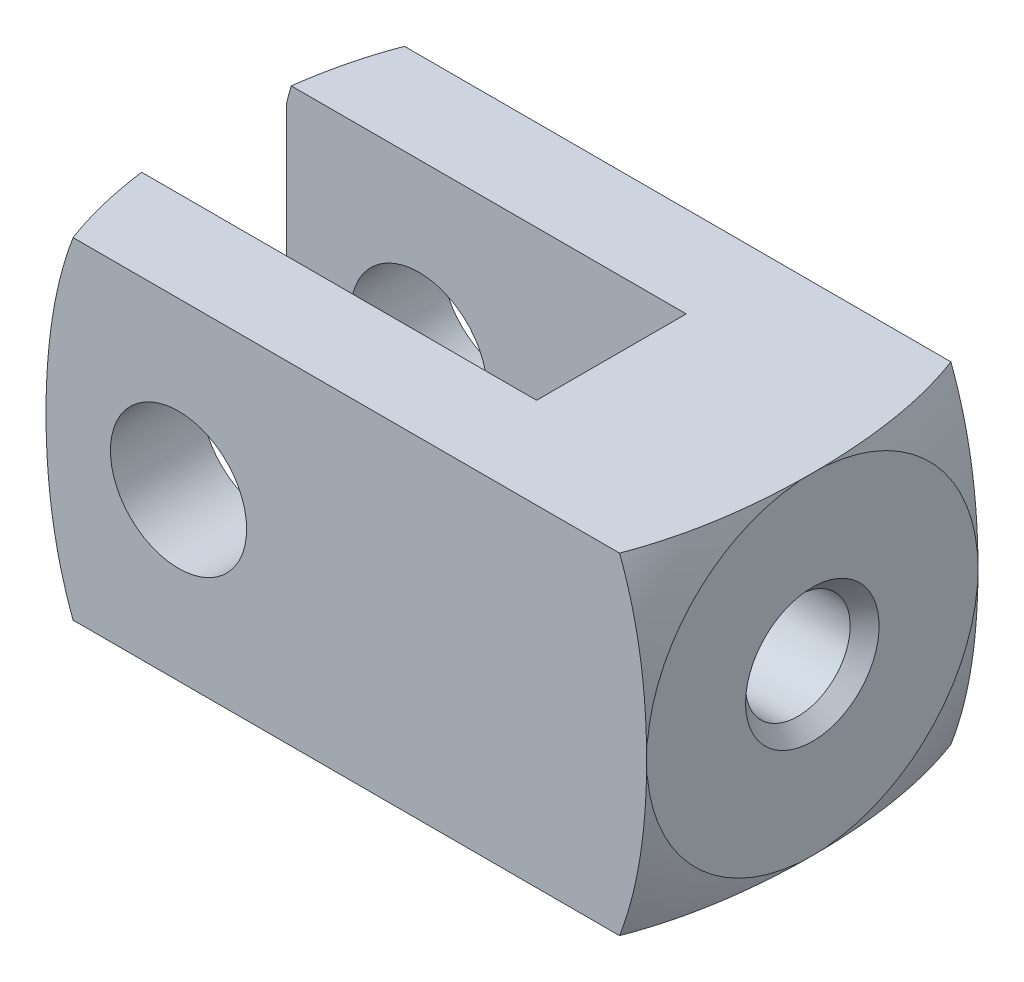
SolidWorks part; units mm, degrees
ref_plane "Front Plane" through (0, 0, 0) normal (0, 0, 1) x (1, 0, 0)
ref_plane "Top Plane" through (0, 0, 0) normal (0, 1, 0) x (1, 0, 0)
ref_plane "Right Plane" through (0, 0, 0) normal (1, 0, 0) x (0, 0, -1)
sketch "Sketch1" plane through (0, 0, 0) normal (0, 0, 1) x (1, 0, 0)
  line L0 (-3.1496, -3.937) -> (11.1252, -3.937)
  line L1 (11.1252, -3.937) -> (11.1252, 3.937)
  line L2 (11.1252, 3.937) -> (-3.1496, 3.937)
  line L3 (-3.1496, 3.937) -> (-3.1496, -3.937)
extrude "Boss-Extrude1" add sketch "Sketch1" against normal blind 3.937 and the other way blind 3.937
sketch "Sketch2" plane through (0, 0, 0) normal (0, 1, 0) x (1, 0, 0)
  line L0 (-3.1496, -1.778) -> (6.35, -1.778)
  line L1 (6.35, -1.778) -> (6.35, 1.778)
  line L2 (6.35, 1.778) -> (-3.1496, 1.778)
  line L3 (-3.1496, 1.778) -> (-3.1496, -1.778)
extrude "Cut-Extrude1" cut sketch "Sketch2" along normal blind 3.937 and the other way blind 3.937
sketch "Sketch3" plane through (0, 0, 0) normal (0, 0, 1) x (1, 0, 0)
  line L0 (6.5532, 0) -> (6.5532, 1.2433)
  line L1 (6.5532, 1.2433) -> (10.781, 1.2433)
  line L2 (10.781, 1.2433) -> (11.1252, 1.5875)
  line L3 (11.1252, 1.5875) -> (11.1252, 0)
  line L4 (11.1252, 0) -> (6.5532, 0)
  line L5 (11.1252, 0) -> (6.5532, 0) construction
revolve "Cut-Revolve1" cut sketch "Sketch3" angle 360 about L5 reverse direction yes
cosmetic thread "Cosmetic Thread1" parameters "D1"=4.572, "D2"=3.175
ref_plane "Plane1" through (0, 0, 6.35) normal (0, 0, 1) x (1, 0, 0)
ref_plane "Plane2" through (0, 0, -6.35) normal (0, 0, 1) x (1, 0, 0)
ref_plane "Plane3" through (23.876, 0, 0) normal (1, 0, 0) x (0, 0, -1)
sketch "Sketch4" plane through (0, 0, 0) normal (0, 0, 1) x (1, 0, 0)
  line L0 (6.35, 0) -> (6.35, 1.2637)
  line L1 (6.35, 1.2637) -> (6.5532, 1.2637)
  line L2 (6.5532, 1.2637) -> (6.5532, 0)
  line L3 (6.5532, 0) -> (6.35, 0)
  line L4 (6.5532, 0) -> (6.35, 0) construction
revolve "Cut-Revolve2" cut sketch "Sketch4" angle 360 about L4 reverse direction yes
sketch "Sketch5" plane through (0, 0, 0) normal (1, 0, 0) x (0, 0, -1)
  line L0 (-3.937, 0) -> (-3.937, 1.6193)
  line L1 (-3.937, 1.6193) -> (3.937, 1.6193)
  line L2 (3.937, 1.6193) -> (3.937, 0)
  line L3 (3.937, 0) -> (-3.937, 0)
  line L4 (3.937, 0) -> (-3.937, 0) construction
revolve "Cut-Revolve3" cut sketch "Sketch5" angle 360 about L4 reverse direction yes
sketch "Sketch6" plane through (0, 0, 0) normal (0, 0, 1) x (1, 0, 0)
  line L0 (11.1252, 0) -> (11.1252, 3.937)
  line L1 (8.5852, 7.874) -> (15.0622, 7.874)
  line L2 (15.0622, 7.874) -> (15.0622, 0)
  line L3 (15.0622, 0) -> (11.1252, 0)
  line L4 (15.0622, 0) -> (11.1252, 0) construction
  arc A0 (11.1252, 3.937) -> (8.5852, 7.874) centre (3.7528, 1.9685) ccw
revolve "Cut-Revolve4" cut sketch "Sketch6" angle 360 about L4 reverse direction yes
sketch "Sketch7" plane through (0, 0, 0) normal (0, 0, 1) x (1, 0, 0)
  line L0 (-7.0866, 0) -> (-7.0866, 7.874)
  line L1 (-7.0866, 7.874) -> (-0.6096, 7.874)
  line L2 (-3.1496, 3.937) -> (-3.1496, 0)
  line L3 (-3.1496, 0) -> (-7.0866, 0)
  line L4 (-3.1496, 0) -> (-7.0866, 0) construction
  arc A0 (-0.6096, 7.874) -> (-3.1496, 3.937) centre (4.2228, 1.9685) ccw
revolve "Cut-Revolve5" cut sketch "Sketch7" angle 360 about L4 reverse direction yes
ref_plane "Plane4" through (11.1252, 0, 0) normal (1, 0, 0) x (0, 0, -1)
ref_plane "Plane5" through (6.35, 0, 0) normal (1, 0, 0) x (0, 0, -1)
ref_plane "dummy XY" through (0, 0, 0) normal (0, 0, 1) x (1, 0, 0)
ref_plane "dummy XZ" through (0, 0, 0) normal (0, -1, 0) x (-1, 0, 0)
ref_plane "dummy YZ" through (0, 0, 0) normal (1, 0, 0) x (0, 0, -1)
ref_axis "dummy X" through (-80.9, 0, 0) along (1, 0, 0)
ref_axis "dummy Y" through (0, -50, 0) along (0, 1, 0)
ref_axis "dummy Z" through (0, 0, 80.9) along (0, 0, -1)
sketch3d "dummy"
  point P0 (0, 0, 0)
ref_plane "h1 XY" through (0, 0, 0) normal (0, 0, 1) x (1, 0, 0)
ref_plane "h1 XZ" through (0, 3.937, 0) normal (0, -1, 0) x (-1, 0, 0)
ref_plane "h1 YZ" through (-3.1496, 0, 0) normal (1, 0, 0) x (0, 0, -1)
ref_axis "h1 X" through (-80.9, 3.937, 0) along (1, 0, 0)
ref_axis "h1 Y" through (-3.1496, -50, 0) along (0, 1, 0)
ref_axis "h1 Z" through (-3.1496, 3.937, 80.9) along (0, 0, -1)
sketch3d "h1"
  point P0 (-3.1496, 3.937, 0)
ref_plane "h2 XY" through (0, 0, 0) normal (0, 0, 1) x (1, 0, 0)
ref_plane "h2 XZ" through (0, -3.937, 0) normal (0, -1, 0) x (-1, 0, 0)
ref_plane "h2 YZ" through (-3.1496, 0, 0) normal (1, 0, 0) x (0, 0, -1)
ref_axis "h2 X" through (-80.9, -3.937, 0) along (1, 0, 0)
ref_axis "h2 Y" through (-3.1496, -50, 0) along (0, 1, 0)
ref_axis "h2 Z" through (-3.1496, -3.937, 80.9) along (0, 0, -1)
sketch3d "h2"
  point P0 (-3.1496, -3.937, 0)
ref_plane "l1 XY" through (0, 0, 0) normal (0, 0, 1) x (1, 0, 0)
ref_plane "l1 XZ" through (0, 3.937, 0) normal (0, -1, 0) x (-1, 0, 0)
ref_plane "l1 YZ" through (11.1252, 0, 0) normal (1, 0, 0) x (0, 0, -1)
ref_axis "l1 X" through (-80.9, 3.937, 0) along (1, 0, 0)
ref_axis "l1 Y" through (11.1252, -50, 0) along (0, 1, 0)
ref_axis "l1 Z" through (11.1252, 3.937, 80.9) along (0, 0, -1)
sketch3d "l1"
  point P0 (11.1252, 3.937, 0)
ref_plane "l11 XY" through (0, 0, 0) normal (0, 0, 1) x (1, 0, 0)
ref_plane "l11 XZ" through (0, 3.937, 0) normal (0, -1, 0) x (-1, 0, 0)
ref_plane "l11 YZ" through (11.1252, 0, 0) normal (1, 0, 0) x (0, 0, -1)
ref_axis "l11 X" through (-80.9, 3.937, 0) along (1, 0, 0)
ref_axis "l11 Y" through (11.1252, -50, 0) along (0, 1, 0)
ref_axis "l11 Z" through (11.1252, 3.937, 80.9) along (0, 0, -1)
sketch3d "l11"
  point P0 (11.1252, 3.937, 0)
ref_plane "l12 XY" through (0, 0, 0) normal (0, 0, 1) x (1, 0, 0)
ref_plane "l12 XZ" through (0, 3.937, 0) normal (0, -1, 0) x (-1, 0, 0)
ref_plane "l12 YZ" through (0, 0, 0) normal (1, 0, 0) x (0, 0, -1)
ref_axis "l12 X" through (-80.9, 3.937, 0) along (1, 0, 0)
ref_axis "l12 Y" through (0, -50, 0) along (0, 1, 0)
ref_axis "l12 Z" through (0, 3.937, 80.9) along (0, 0, -1)
sketch3d "l12"
  point P0 (0, 3.937, 0)
ref_plane "l2 XY" through (0, 0, 0) normal (0, 0, 1) x (1, 0, 0)
ref_plane "l2 XZ" through (0, 3.937, 0) normal (0, -1, 0) x (-1, 0, 0)
ref_plane "l2 YZ" through (-3.1496, 0, 0) normal (1, 0, 0) x (0, 0, -1)
ref_axis "l2 X" through (-80.9, 3.937, 0) along (1, 0, 0)
ref_axis "l2 Y" through (-3.1496, -50, 0) along (0, 1, 0)
ref_axis "l2 Z" through (-3.1496, 3.937, 80.9) along (0, 0, -1)
sketch3d "l2"
  point P0 (-3.1496, 3.937, 0)
ref_plane "l21 XY" through (0, 0, 0) normal (0, 1, 0) x (1, 0, 0)
ref_plane "l21 XZ" through (0, 0, 0) normal (0, 0, 1) x (1, 0, 0)
ref_plane "l21 YZ" through (11.1252, 0, 0) normal (1, 0, 0) x (0, 0, -1)
ref_axis "l21 X" through (-80.9, 0, 0) along (1, 0, 0)
ref_axis "l21 Y" through (11.1252, 0, 50) along (0, 0, -1)
ref_axis "l21 Z" through (11.1252, 50, 0) along (0, -1, 0)
sketch3d "l21"
  point P0 (11.1252, 0, 0)
ref_plane "l22 XY" through (0, 0, 0) normal (0, 1, 0) x (1, 0, 0)
ref_plane "l22 XZ" through (0, 0, 0) normal (0, 0, 1) x (1, 0, 0)
ref_plane "l22 YZ" through (6.35, 0, 0) normal (1, 0, 0) x (0, 0, -1)
ref_axis "l22 X" through (-80.9, 0, 0) along (1, 0, 0)
ref_axis "l22 Y" through (6.35, 0, 50) along (0, 0, -1)
ref_axis "l22 Z" through (6.35, 50, 0) along (0, -1, 0)
sketch3d "l22"
  point P0 (6.35, 0, 0)
ref_plane "piston_rod_clevis XY" through (11.1252, 0, 0) normal (1, 0, 0) x (0, 0, -1)
ref_plane "piston_rod_clevis XZ" through (0, 0, 0) normal (0, -1, 0) x (-1, 0, 0)
ref_plane "piston_rod_clevis YZ" through (0, 0, 0) normal (0, 0, -1) x (-1, 0, 0)
ref_axis "piston_rod_clevis X" through (11.1252, 0, 80.9) along (0, 0, -1)
ref_axis "piston_rod_clevis Y" through (11.1252, -50, 0) along (0, 1, 0)
ref_axis "piston_rod_clevis Z" through (80.9, 0, 0) along (-1, 0, 0)
sketch3d "piston_rod_clevis"
  point P0 (11.1252, 0, 0)
ref_plane "rod_clevis_body XY" through (0, 0, 0) normal (0, 0, 1) x (1, 0, 0)
ref_plane "rod_clevis_body XZ" through (0, 0, 0) normal (0, -1, 0) x (-1, 0, 0)
ref_plane "rod_clevis_body YZ" through (0, 0, 0) normal (1, 0, 0) x (0, 0, -1)
ref_axis "rod_clevis_body X" through (-80.9, 0, 0) along (1, 0, 0)
ref_axis "rod_clevis_body Y" through (0, -50, 0) along (0, 1, 0)
ref_axis "rod_clevis_body Z" through (0, 0, 80.9) along (0, 0, -1)
sketch3d "rod_clevis_body"
  point P0 (0, 0, 0)
ref_plane "th1 XY" through (0, 0, 0) normal (0, 0, 1) x (1, 0, 0)
ref_plane "th1 XZ" through (0, 1.5875, 0) normal (0, -1, 0) x (-1, 0, 0)
ref_plane "th1 YZ" through (11.1252, 0, 0) normal (1, 0, 0) x (0, 0, -1)
ref_axis "th1 X" through (-80.9, 1.5875, 0) along (1, 0, 0)
ref_axis "th1 Y" through (11.1252, -50, 0) along (0, 1, 0)
ref_axis "th1 Z" through (11.1252, 1.5875, 80.9) along (0, 0, -1)
sketch3d "th1"
  point P0 (11.1252, 1.5875, 0)
ref_plane "th2 XY" through (0, 0, 0) normal (0, 0, 1) x (1, 0, 0)
ref_plane "th2 XZ" through (0, -1.5875, 0) normal (0, -1, 0) x (-1, 0, 0)
ref_plane "th2 YZ" through (11.1252, 0, 0) normal (1, 0, 0) x (0, 0, -1)
ref_axis "th2 X" through (-80.9, -1.5875, 0) along (1, 0, 0)
ref_axis "th2 Y" through (11.1252, -50, 0) along (0, 1, 0)
ref_axis "th2 Z" through (11.1252, -1.5875, 80.9) along (0, 0, -1)
sketch3d "th2"
  point P0 (11.1252, -1.5875, 0)
ref_plane "to_cylinder XY" through (6.35, 0, 0) normal (1, 0, 0) x (0, 0, -1)
ref_plane "to_cylinder XZ" through (0, 0, 0) normal (0, -1, 0) x (-1, 0, 0)
ref_plane "to_cylinder YZ" through (0, 0, 0) normal (0, 0, -1) x (-1, 0, 0)
ref_axis "to_cylinder X" through (6.35, 0, 80.9) along (0, 0, -1)
ref_axis "to_cylinder Y" through (6.35, -50, 0) along (0, 1, 0)
ref_axis "to_cylinder Z" through (80.9, 0, 0) along (-1, 0, 0)
sketch3d "to_cylinder"
  point P0 (6.35, 0, 0)
ref_plane "w1 XY" through (0, 0, 0) normal (0, 1, 0) x (1, 0, 0)
ref_plane "w1 XZ" through (0, 0, -3.937) normal (0, 0, 1) x (1, 0, 0)
ref_plane "w1 YZ" through (11.1252, 0, 0) normal (1, 0, 0) x (0, 0, -1)
ref_axis "w1 X" through (-80.9, 0, -3.937) along (1, 0, 0)
ref_axis "w1 Y" through (11.1252, 0, 50) along (0, 0, -1)
ref_axis "w1 Z" through (11.1252, 50, -3.937) along (0, -1, 0)
sketch3d "w1"
  point P0 (11.1252, 0, -3.937)
ref_plane "w11 XY" through (0, 0, 0) normal (0, 1, 0) x (1, 0, 0)
ref_plane "w11 XZ" through (0, 0, -1.778) normal (0, 0, 1) x (1, 0, 0)
ref_plane "w11 YZ" through (-3.1496, 0, 0) normal (1, 0, 0) x (0, 0, -1)
ref_axis "w11 X" through (-80.9, 0, -1.778) along (1, 0, 0)
ref_axis "w11 Y" through (-3.1496, 0, 50) along (0, 0, -1)
ref_axis "w11 Z" through (-3.1496, 50, -1.778) along (0, -1, 0)
sketch3d "w11"
  point P0 (-3.1496, 0, -1.778)
ref_plane "w12 XY" through (0, 0, 0) normal (0, 1, 0) x (1, 0, 0)
ref_plane "w12 XZ" through (0, 0, 1.778) normal (0, 0, 1) x (1, 0, 0)
ref_plane "w12 YZ" through (-3.1496, 0, 0) normal (1, 0, 0) x (0, 0, -1)
ref_axis "w12 X" through (-80.9, 0, 1.778) along (1, 0, 0)
ref_axis "w12 Y" through (-3.1496, 0, 50) along (0, 0, -1)
ref_axis "w12 Z" through (-3.1496, 50, 1.778) along (0, -1, 0)
sketch3d "w12"
  point P0 (-3.1496, 0, 1.778)
ref_plane "w2 XY" through (0, 0, 0) normal (0, 1, 0) x (1, 0, 0)
ref_plane "w2 XZ" through (0, 0, 3.937) normal (0, 0, 1) x (1, 0, 0)
ref_plane "w2 YZ" through (11.1252, 0, 0) normal (1, 0, 0) x (0, 0, -1)
ref_axis "w2 X" through (-80.9, 0, 3.937) along (1, 0, 0)
ref_axis "w2 Y" through (11.1252, 0, 50) along (0, 0, -1)
ref_axis "w2 Z" through (11.1252, 50, 3.937) along (0, -1, 0)
sketch3d "w2"
  point P0 (11.1252, 0, 3.937)
